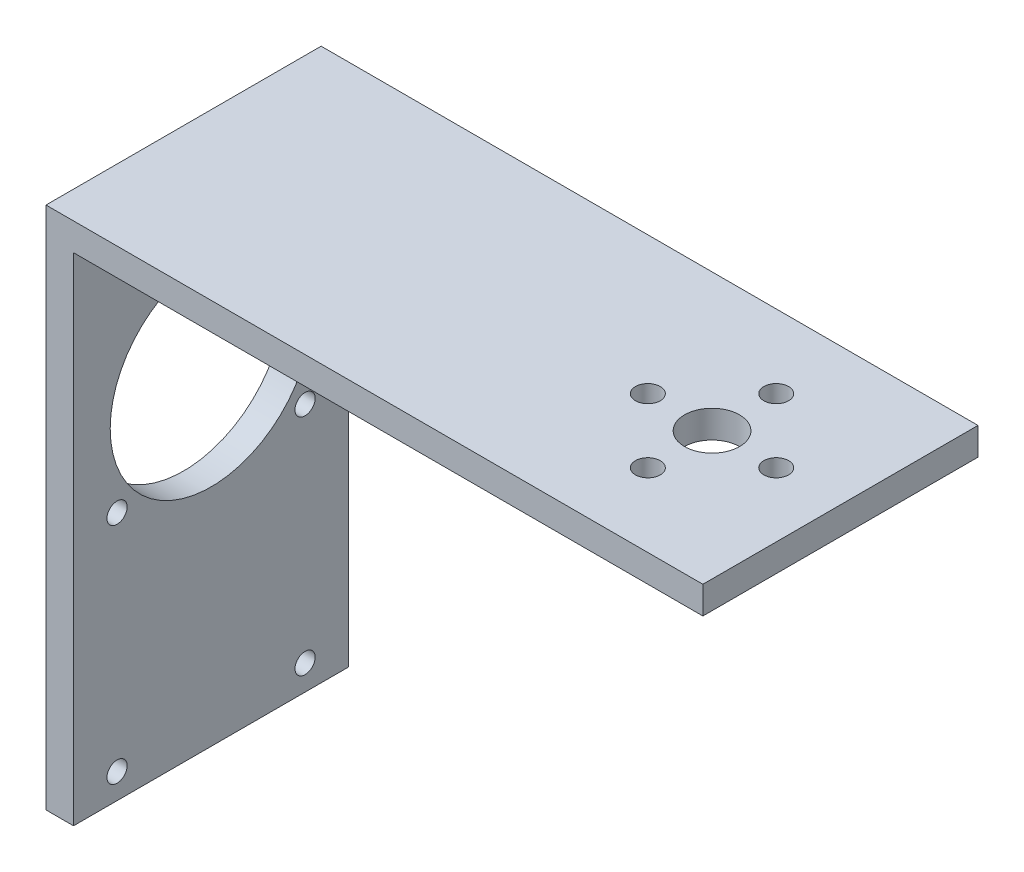
SolidWorks part; units mm, degrees
ref_plane "Front Plane" through (0, 0, 0) normal (0, 0, 1) x (1, 0, 0)
ref_plane "Top Plane" through (0, 0, 0) normal (0, 1, 0) x (1, 0, 0)
ref_plane "Right Plane" through (0, 0, 0) normal (1, 0, 0) x (0, 0, -1)
ref_plane "PZ_m15_000" through (0, 0, -15) normal (0, 0, 1) x (1, 0, 0)
sketch "S_box1" plane through (0, 0, -15) normal (0, 0, 1) x (1, 0, 0)
  line L0 (-57.625, 18.625) -> (14, 18.625)
  line L1 (14, 18.625) -> (14, 21.625)
  line L2 (14, 21.625) -> (-57.625, 21.625)
  line L3 (-57.625, 21.625) -> (-57.625, 18.625)
  dimension "P1" = 57.625
  dimension "P2" = 18.625
  dimension "P3" = 14
  dimension "P4" = 18.625
  dimension "P5" = 14
  dimension "P6" = 21.625
  dimension "P7" = 57.625
  dimension "P8" = 21.625
extrude "Boss_1" add sketch "S_box1" along normal blind 30
sketch "S_box2" plane through (0, 0, -15) normal (0, 0, 1) x (1, 0, 0)
  line L0 (-57.625, -35.5) -> (-54.625, -35.5)
  line L1 (-54.625, -35.5) -> (-54.625, 19.125)
  line L2 (-54.625, 19.125) -> (-57.625, 19.125)
  line L3 (-57.625, 19.125) -> (-57.625, -35.5)
  dimension "P1" = 57.625
  dimension "P2" = 35.5
  dimension "P3" = 54.625
  dimension "P4" = 35.5
  dimension "P5" = 54.625
  dimension "P6" = 19.125
  dimension "P7" = 57.625
  dimension "P8" = 19.125
extrude "Boss_2" add sketch "S_box2" along normal blind 30
sketch "S_box3" plane through (0, 0, -15) normal (0, 0, 1) x (1, 0, 0)
  line L0 (-55.125, 15.625) -> (-24, 15.625)
  line L1 (-24, 15.625) -> (-24, 19.125)
  line L2 (-24, 19.125) -> (-55.125, 19.125)
  line L3 (-55.125, 19.125) -> (-55.125, 15.625)
  dimension "P1" = 55.125
  dimension "P2" = 15.625
  dimension "P3" = 24
  dimension "P4" = 15.625
  dimension "P5" = 24
  dimension "P6" = 19.125
  dimension "P7" = 55.125
  dimension "P8" = 19.125
extrude "Boss_3" add sketch "S_box3" along normal blind 3
ref_plane "PY_p18_525" through (0, 18.525, 0) normal (0, 1, 0) x (1, 0, 0)
sketch "S_hole4" plane through (0, 18.525, 0) normal (0, 1, 0) x (1, 0, 0)
  circle A0 centre (0, 0) radius 3
  dimension "D1_S_hole4" = 6
extrude "Hole_4" cut sketch "S_hole4" along normal blind 3.2
sketch "S_hole5" plane through (0, 18.525, 0) normal (0, 1, 0) x (1, 0, 0)
  circle A0 centre (7, 0) radius 1.35
  dimension "D1_S_hole5" = 2.7
  dimension "P2" = 7
extrude "Hole_5" cut sketch "S_hole5" along normal blind 3.2
sketch "S_hole6" plane through (0, 18.525, 0) normal (0, 1, 0) x (1, 0, 0)
  circle A0 centre (0, -7) radius 1.35
  dimension "D1_S_hole6" = 2.7
  dimension "P2" = 7
extrude "Hole_6" cut sketch "S_hole6" along normal blind 3.2
sketch "S_hole7" plane through (0, 18.525, 0) normal (0, 1, 0) x (1, 0, 0)
  circle A0 centre (-7, 0) radius 1.35
  dimension "D1_S_hole7" = 2.7
  dimension "P2" = 7
extrude "Hole_7" cut sketch "S_hole7" along normal blind 3.2
sketch "S_hole8" plane through (0, 18.525, 0) normal (0, 1, 0) x (1, 0, 0)
  circle A0 centre (0, 7) radius 1.35
  dimension "D1_S_hole8" = 2.7
  dimension "P2" = 7
extrude "Hole_8" cut sketch "S_hole8" along normal blind 3.2
ref_plane "PX_m57_725" through (-57.725, 0, 0) normal (1, 0, 0) x (0, 0, -1)
sketch "S_hole9" plane through (-57.725, 0, 0) normal (1, 0, 0) x (0, 0, -1)
  circle A0 centre (0, 0) radius 11
  dimension "D1_S_hole9" = 22
extrude "Hole_9" cut sketch "S_hole9" along normal blind 3.2
sketch "S_hole10" plane through (-57.725, 0, 0) normal (1, 0, 0) x (0, 0, -1)
  circle A0 centre (10.25, -8.3) radius 1.1
  dimension "D1_S_hole10" = 2.2
  dimension "P2" = 10.25
  dimension "P3" = 8.3
extrude "Hole_10" cut sketch "S_hole10" along normal blind 3.2
sketch "S_hole11" plane through (-57.725, 0, 0) normal (1, 0, 0) x (0, 0, -1)
  circle A0 centre (-10.25, -8.3) radius 1.1
  dimension "D1_S_hole11" = 2.2
  dimension "P2" = 10.25
  dimension "P3" = 8.3
extrude "Hole_11" cut sketch "S_hole11" along normal blind 3.2
sketch "S_hole12" plane through (-57.725, 0, 0) normal (1, 0, 0) x (0, 0, -1)
  circle A0 centre (10.25, -32.75) radius 1.1
  dimension "D1_S_hole12" = 2.2
  dimension "P2" = 10.25
  dimension "P3" = 32.75
extrude "Hole_12" cut sketch "S_hole12" along normal blind 3.2
sketch "S_hole13" plane through (-57.725, 0, 0) normal (1, 0, 0) x (0, 0, -1)
  circle A0 centre (-10.25, -32.75) radius 1.1
  dimension "D1_S_hole13" = 2.2
  dimension "P2" = 10.25
  dimension "P3" = 32.75
extrude "Hole_13" cut sketch "S_hole13" along normal blind 3.2
equation "\"plate_t\" = 3"
equation "\"clearance\" = 0.4"
